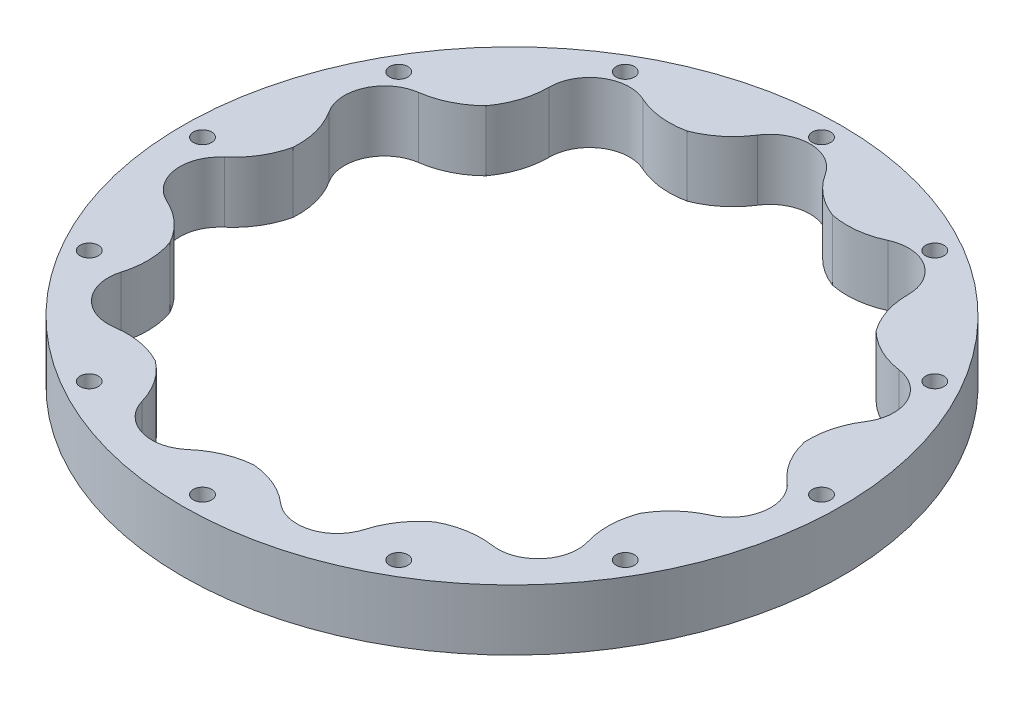
SolidWorks part; units mm, degrees
ref_plane "Front Plane" through (0, 0, 0) normal (0, 0, 1) x (1, 0, 0)
ref_plane "Top Plane" through (0, 0, 0) normal (0, 1, 0) x (1, 0, 0)
ref_plane "Right Plane" through (0, 0, 0) normal (1, 0, 0) x (0, 0, -1)
sketch "Sketch1" plane through (0, 0, 0) normal (0, 1, 0) x (1, 0, 0)
  circle A0 centre (0, 0) radius 45
  circle A1 centre (0, 45) radius 7
  circle A2 centre (24.3288, 37.8564) radius 7
  circle A3 centre (40.9334, 18.6937) radius 7
  circle A4 centre (44.542, -6.4042) radius 7
  circle A5 centre (34.0087, -29.4687) radius 7
  circle A6 centre (12.678, -43.1772) radius 7
  circle A7 centre (-12.678, -43.1772) radius 7
  circle A8 centre (-34.0087, -29.4687) radius 7
  circle A9 centre (-44.542, -6.4042) radius 7
  circle A10 centre (-40.9334, 18.6937) radius 7
  circle A11 centre (-24.3288, 37.8564) radius 7
  circle A12 centre (0, 0) radius 57.5
  circle A13 centre (0, 0) radius 54 construction
  circle A14 centre (0, 54) radius 1.6
  circle A15 centre (27, 46.7654) radius 1.6
  circle A16 centre (46.7654, 27) radius 1.6
  circle A17 centre (54, 0) radius 1.6
  circle A18 centre (46.7654, -27) radius 1.6
  circle A19 centre (27, -46.7654) radius 1.6
  circle A20 centre (0, -54) radius 1.6
  circle A21 centre (-27, -46.7654) radius 1.6
  circle A22 centre (-46.7654, -27) radius 1.6
  circle A23 centre (-54, 0) radius 1.6
  circle A24 centre (-46.7654, 27) radius 1.6
  circle A25 centre (-27, 46.7654) radius 1.6
  point P27 (0, 0)
  point P54 (0, 0)
  dimension "D1" = 90
  dimension "D2" = 14
  dimension "D4" = 115
  dimension "D5" = 108
  dimension "D6" = 3.2
  dimension "D3" = 11
  dimension "D7" = 12
extrude "Boss-Extrude1" add sketch "Sketch1" along normal blind 10.6 contours A12 A25 A24 A23 A22 A21 A20 A19 A18 A17 A16 A15 A14 A11 A0 A1 A2 A3 A4 A5 A6 A7 A8 A9 A10 region at (-55.8737, 0, 0)
fillet "Fillet1" radius 14 22 edges at (44.9962, 5.3, -0.5811) (43.3373, 5.3, -12.1194) (38.1674, 5.3, 23.838) (43.0099, 5.3, 13.2344) (29.0271, 5.3, 34.3864) (19.2207, 5.3, 40.6886) (5.8285, 5.3, 44.6209) (-5.8285, 5.3, 44.6209) (-19.2207, 5.3, 40.6886) (-29.0271, 5.3, 34.3864) (-43.0099, 5.3, 13.2344) (-38.1674, 5.3, 23.838) (-44.9962, 5.3, -0.5811) (-43.3373, 5.3, -12.1194) (-37.5391, 5.3, -24.8156) (-29.9054, 5.3, -33.6254) (37.5391, 5.3, -24.8156) (29.9054, 5.3, -33.6254) (18.1636, 5.3, -41.1714) (6.9788, 5.3, -44.4556) (-6.9788, 5.3, -44.4556) (-18.1636, 5.3, -41.1714)
